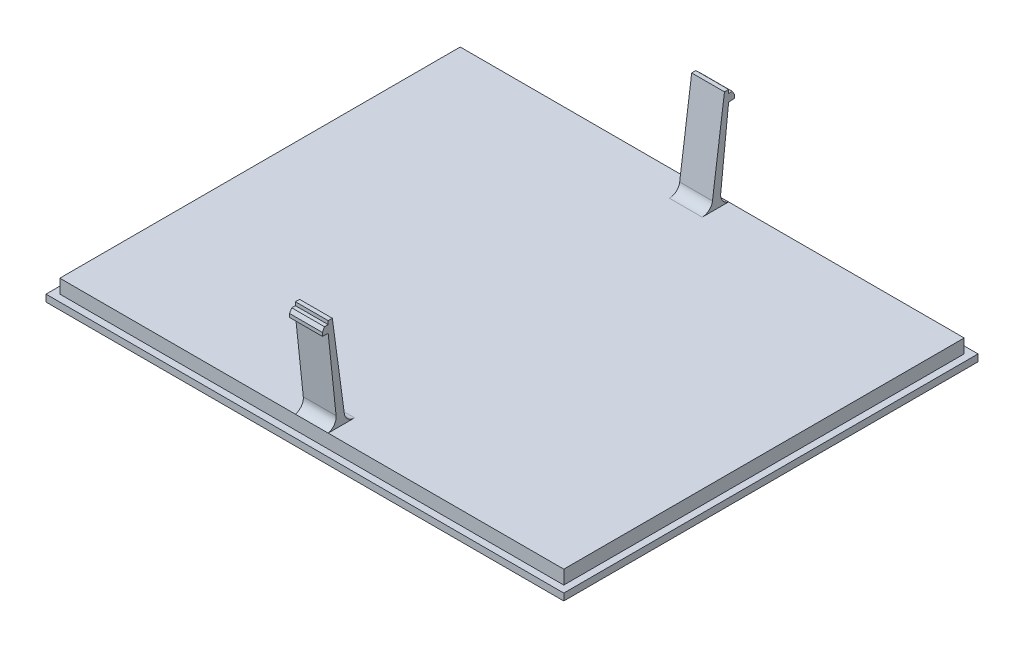
SolidWorks part; units mm, degrees
other "Markup1"
sketch "Sketch5" plane through (-105, 0, 60.5) normal (-0.0451, -0.9984, 0.0353) x (-0.7444, 0.01, -0.6676)
other "Markup2"
sketch "Sketch6" plane through (97, 11, -60) normal (0.0014, 0.7787, -0.6274) x (0.9996, 0.0165, 0.0227)
ref_plane "Front Plane" through (0, 0, 0) normal (0, 0, 1) x (1, 0, 0)
ref_plane "Top Plane" through (0, 0, 0) normal (0, 1, 0) x (1, 0, 0)
ref_plane "Right Plane" through (0, 0, 0) normal (1, 0, 0) x (0, 0, -1)
sketch "Sketch1" plane through (0, 0, 0) normal (0, 1, 0) x (1, 0, 0)
  line L1 (-75, 60) -> (75, 60)
  line L2 (-75, 60) -> (-75, -60)
  line L3 (-75, -60) -> (75, -60)
  line L4 (75, 60) -> (75, -60)
  point P4 (0, 60)
  point P5 (-75, 0)
  dimension "D1" = 120
  dimension "D2" = 150
extrude "Top" add sketch "Sketch1" along normal blind 2
sketch "Sketch2" plane through (0, 2, 0) normal (0, 1, 0) x (1, 0, 0)
  line L1 (-73, -58) -> (73, -58)
  line L2 (-73, -58) -> (-73, 58)
  line L3 (-73, 58) -> (73, 58)
  line L4 (73, -58) -> (73, 58)
  point P4 (0, 58)
  point P7 (73, 0)
  dimension "D1" = 116
  dimension "D2" = 146
extrude "Bottom" add sketch "Sketch2" along normal blind 4
sketch "Sketch7" plane through (0, 0, 0) normal (1, 0, 0) x (0, 0, -1)
  line L0 (-55.3724, 6) -> (-52.9724, 6)
  line L1 (-58, 6) -> (58, 6) construction
  line L2 (-52.9724, 6) -> (-56.8, 34.2199)
  line L4 (-59.06, 33.2199) -> (-59.6959, 32.1186)
  line L5 (-59.6959, 32.1186) -> (-59.6959, 31.1186)
  line L6 (-59.6959, 31.1186) -> (-58, 31)
  line L7 (-58, 31) -> (-55.3724, 6)
  line L8 (-60, 2) -> (-60, 36.7843) construction
  line L9 (-58, 6) -> (-58, 37.1212) construction
  line L10 (-58, 33.2199) -> (-59.06, 33.2199)
  line L12 (-58, 33.2199) -> (-58, 34.2199)
  line L16 (-58, 34.2199) -> (-56.8, 34.2199)
  dimension "D1" = 2.4
  dimension "D2" = 1.7
  dimension "D3" = 100
  dimension "D4" = 1.2
  dimension "D5" = 30
  dimension "D6" = 25
  dimension "D7" = 1
  dimension "D8" = 96
  dimension "D9" = 1.06
extrude "Boss-Extrude1" add sketch "Sketch7" along normal mid plane 9.5
fillet "Fillet1" radius 3 2 edges at (0, 6, 52.9724) (0, 6, 55.3724)
mirror "Mirror1" about plane through (0, 0, 0) normal (0, 0, 1) of "Fillet1", "Boss-Extrude1"
